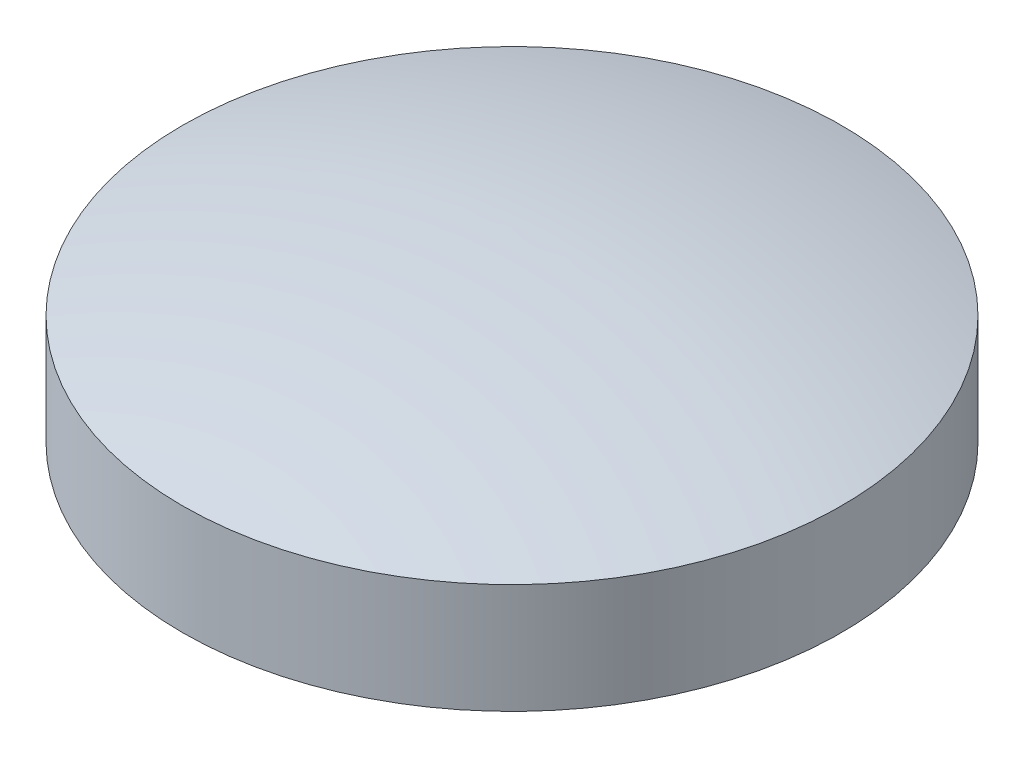
SolidWorks part; units mm, degrees
material "玻璃"
ref_plane "前视基准面" through (0, 0, 0) normal (0, 0, 1) x (1, 0, 0)
ref_plane "上视基准面" through (0, 0, 0) normal (0, 1, 0) x (1, 0, 0)
ref_plane "右视基准面" through (0, 0, 0) normal (1, 0, 0) x (0, 0, -1)
sketch "草图1" plane through (0, 0, 0) normal (0, 0, 1) x (1, 0, 0)
  line L0 (0, 1.1078) -> (0, -1.0527) construction
  line L1 (-1.8, 0.3) -> (1.8, 0.3)
  line L2 (-1.8, 0.3) -> (-1.8, -0.3)
  line L3 (-1.8, -0.3) -> (1.8, -0.3)
  line L4 (1.8, 0.3) -> (1.8, -0.3)
  line L5 (-1.8, 0.3) -> (1.8, -0.3) construction
  line L6 (-1.8, -0.3) -> (1.8, 0.3) construction
  line L7 (0, 0.5764) -> (0, -0.5764)
  arc A0 (-1.8, 0.3) -> (1.8, 0.3) centre (0, -5.4236) cw
  arc A1 (-1.8, -0.3) -> (1.8, -0.3) centre (0, 5.4236) ccw
  point P0 (0, 0)
  dimension "D2" = 6
  dimension "D3" = 6
  dimension "D1" = 0.6
  dimension "D4" = 3.6
revolve "旋转1" add sketch "草图1" angle 360 about L0 region at (-0.6771, 0.4108, 0) region at (-0.9, 0, 0) region at (-0.6771, -0.4108, 0)
